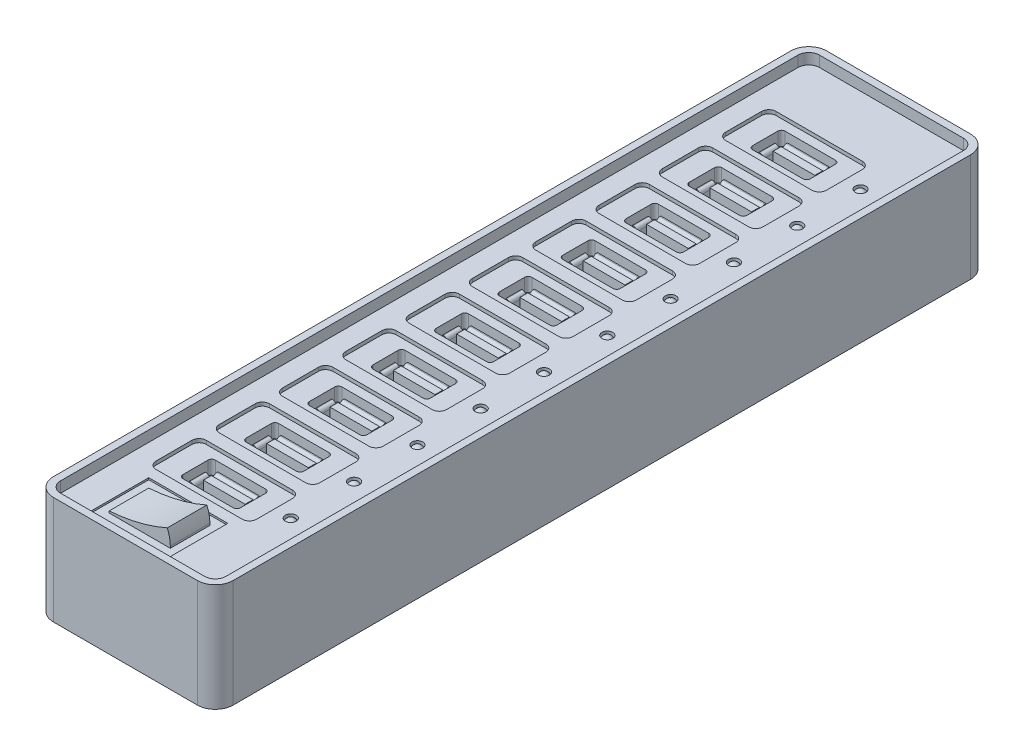
SolidWorks part; units mm, degrees
ref_plane "정면" through (0, 0, 0) normal (0, 0, 1) x (1, 0, 0)
ref_plane "윗면" through (0, 0, 0) normal (0, 1, 0) x (1, 0, 0)
ref_plane "우측면" through (0, 0, 0) normal (1, 0, 0) x (0, 0, -1)
sketch "스케치1" plane through (0, 0, 0) normal (0, 1, 0) x (1, 0, 0)
  line L1 (-20, -107.5) -> (20, -107.5)
  line L2 (-25, -102.5) -> (-25, 102.5)
  line L3 (-20, 107.5) -> (20, 107.5)
  line L4 (25, -102.5) -> (25, 102.5)
  line L5 (-25, -107.5) -> (25, 107.5) construction
  line L6 (-25, 107.5) -> (25, -107.5) construction
  arc A0 (20, -107.5) -> (25, -102.5) centre (20, -102.5) ccw
  arc A1 (-20, -107.5) -> (-25, -102.5) centre (-20, -102.5) cw
  arc A2 (20, 107.5) -> (25, 102.5) centre (20, 102.5) cw
  arc A3 (-25, 102.5) -> (-20, 107.5) centre (-20, 102.5) cw
  point P0 (0, 0)
  dimension "D3" = 5
  dimension "D1" = 215
  dimension "D2" = 50
extrude "보스-돌출1" add sketch "스케치1" along normal blind 30
sketch "스케치2" plane through (0, 30, 0) normal (0, 1, 0) x (1, 0, 0)
  line L0 (23, -102.5) -> (23, 102.5)
  line L1 (20, 105.5) -> (-20, 105.5)
  line L2 (-23, 102.5) -> (-23, -102.5)
  line L3 (-20, -105.5) -> (20, -105.5)
  arc A0 (20, -105.5) -> (23, -102.5) centre (20, -102.5) ccw
  arc A1 (23, 102.5) -> (20, 105.5) centre (20, 102.5) ccw
  arc A2 (-20, 105.5) -> (-23, 102.5) centre (-20, 102.5) ccw
  arc A3 (-23, -102.5) -> (-20, -105.5) centre (-20, -102.5) ccw
extrude "컷-돌출1" cut sketch "스케치2" against normal blind 3
sketch "스케치3" plane through (0, 27, 0) normal (0, 1, 0) x (1, 0, 0)
  line L0 (-25, 102.5) -> (-25, -102.5) construction
  line L1 (-15.5, -69.5) -> (8.5, -69.5)
  line L2 (-17.5, -71.5) -> (-17.5, -81.5)
  line L3 (-15.5, -83.5) -> (8.5, -83.5)
  line L4 (10.5, -71.5) -> (10.5, -81.5)
  line L5 (-17.5, -69.5) -> (10.5, -83.5) construction
  line L6 (-17.5, -83.5) -> (10.5, -69.5) construction
  line L7 (-20, -107.5) -> (20, -107.5) construction
  arc A0 (8.5, -83.5) -> (10.5, -81.5) centre (8.5, -81.5) ccw
  arc A1 (-17.5, -81.5) -> (-15.5, -83.5) centre (-15.5, -81.5) ccw
  arc A2 (8.5, -69.5) -> (10.5, -71.5) centre (8.5, -71.5) cw
  arc A3 (-15.5, -69.5) -> (-17.5, -71.5) centre (-15.5, -71.5) ccw
  point P0 (-3.5, -76.5)
  dimension "D5" = 2
  dimension "D1" = 28
  dimension "D2" = 14
  dimension "D3" = 7.5
  dimension "D4" = 24
extrude "컷-돌출2" cut sketch "스케치3" against normal blind 1
sketch "스케치4" plane through (0, 26, 0) normal (0, 1, 0) x (1, 0, 0)
  line L0 (10.5, -81.5) -> (10.5, -71.5) construction
  line L1 (-10.5, -72) -> (3.5, -72)
  line L2 (-11.5, -73) -> (-11.5, -80)
  line L3 (-10.5, -81) -> (3.5, -81)
  line L4 (4.5, -73) -> (4.5, -80)
  line L5 (-11.5, -72) -> (4.5, -81) construction
  line L6 (-11.5, -81) -> (4.5, -72) construction
  line L7 (-15.5, -83.5) -> (8.5, -83.5) construction
  arc A0 (3.5, -72) -> (4.5, -73) centre (3.5, -73) cw
  arc A1 (3.5, -81) -> (4.5, -80) centre (3.5, -80) ccw
  arc A2 (-11.5, -80) -> (-10.5, -81) centre (-10.5, -80) ccw
  arc A3 (-11.5, -73) -> (-10.5, -72) centre (-10.5, -73) cw
  point P0 (-3.5, -76.5)
  point P5 (4.5, -76.5)
  point P8 (10.5, -76.5)
  point P9 (-3.5, -72)
  point P12 (-3.5, -83.5)
  dimension "D3" = 1
  dimension "D1" = 16
  dimension "D2" = 9
extrude "컷-돌출3" cut sketch "스케치4" against normal blind 2
sketch "스케치5" plane through (0, 24, 0) normal (0, 1, 0) x (1, 0, 0)
  line L0 (2.3, -72.5) -> (-9.3, -72.5)
  line L1 (-11, -74.3) -> (-11, -78.7)
  line L2 (-9.3, -80.5) -> (2.3, -80.5)
  line L3 (4, -78.7) -> (4, -74.3)
  line L4 (3.5, -72) -> (-10.5, -72)
  line L5 (-11.5, -73) -> (-11.5, -80)
  line L6 (-10.5, -81) -> (3.5, -81)
  line L7 (4.5, -80) -> (4.5, -73)
  line L8 (3.5, -72) -> (-10.5, -72)
  line L9 (-11.5, -73) -> (-11.5, -80)
  line L10 (-10.5, -81) -> (3.5, -81)
  line L11 (4.5, -80) -> (4.5, -73)
  line L12 (-10, -74.3) -> (-11, -74.3)
  line L13 (-9.3, -79.2) -> (2.3, -79.2)
  line L14 (-9.8, -78.7) -> (-9.8, -74.3)
  line L15 (-9.3, -73.8) -> (2.3, -73.8)
  line L16 (2.8, -78.7) -> (2.8, -74.3)
  line L17 (-9.8, -79.2) -> (2.8, -73.8) construction
  line L18 (-9.8, -73.8) -> (2.8, -79.2) construction
  line L19 (-9.3, -73.6) -> (-9.3, -72.5)
  line L20 (-10, -78.7) -> (-11, -78.7)
  line L21 (-9.3, -79.4) -> (-9.3, -80.5)
  line L22 (2.3, -79.4) -> (2.3, -80.5)
  line L23 (3, -78.7) -> (4, -78.7)
  line L24 (3, -74.3) -> (4, -74.3)
  line L25 (2.3, -73.6) -> (2.3, -72.5)
  line L27 (3.5, -72.5) -> (-10.5, -72.5) construction
  line L28 (-11, -73) -> (-11, -80) construction
  line L29 (-10.5, -80.5) -> (3.5, -80.5) construction
  line L30 (4, -80) -> (4, -73) construction
  line L35 (-9.3, -76.5) -> (2.3, -78.7) construction
  line L36 (-9.3, -78.7) -> (2.3, -76.5) construction
  line L37 (-9.3, -76.5) -> (2.3, -76.5)
  line L38 (-9.3, -76.5) -> (-9.3, -74.3)
  line L39 (-9.3, -74.3) -> (2.3, -74.3)
  line L40 (2.3, -76.5) -> (2.3, -74.3)
  line L41 (-9.3, -76.5) -> (2.3, -74.3) construction
  line L42 (-9.3, -74.3) -> (2.3, -76.5) construction
  arc A4 (4.5, -73) -> (3.5, -72) centre (3.5, -73) ccw
  arc A5 (-10.5, -72) -> (-11.5, -73) centre (-10.5, -73) ccw
  arc A6 (-11.5, -80) -> (-10.5, -81) centre (-10.5, -80) ccw
  arc A7 (3.5, -81) -> (4.5, -80) centre (3.5, -80) ccw
  arc A8 (4.5, -73) -> (3.5, -72) centre (3.5, -73) ccw
  arc A9 (-10.5, -72) -> (-11.5, -73) centre (-10.5, -73) ccw
  arc A10 (-11.5, -80) -> (-10.5, -81) centre (-10.5, -80) ccw
  arc A11 (3.5, -81) -> (4.5, -80) centre (3.5, -80) ccw
  arc A12 (2.3, -73.8) -> (2.8, -74.3) centre (2.3, -74.3) cw
  arc A13 (2.3, -79.2) -> (2.8, -78.7) centre (2.3, -78.7) ccw
  arc A14 (-9.3, -79.2) -> (-9.8, -78.7) centre (-9.3, -78.7) cw
  arc A15 (-9.8, -74.3) -> (-9.3, -73.8) centre (-9.3, -74.3) cw
  arc A16 (-10.5, -72.5) -> (-11, -73) centre (-10.5, -73) ccw construction
  arc A17 (-11, -80) -> (-10.5, -80.5) centre (-10.5, -80) ccw construction
  arc A18 (3.5, -80.5) -> (4, -80) centre (3.5, -80) ccw construction
  arc A19 (4, -73) -> (3.5, -72.5) centre (3.5, -73) ccw construction
  arc A20 (-10, -74.3) -> (-9.3, -73.6) centre (-9.3, -74.3) cw
  arc A21 (-9.3, -79.4) -> (-10, -78.7) centre (-9.3, -78.7) cw
  arc A22 (2.3, -73.6) -> (3, -74.3) centre (2.3, -74.3) cw
  arc A23 (2.3, -79.4) -> (3, -78.7) centre (2.3, -78.7) ccw
  point P24 (-3.5, -76.5)
  point P30 (-3.5, -77.6)
  point P64 (-3.5, -76.5)
  point P65 (-3.5, -75.4)
  dimension "D5" = 0.5
  dimension "D3" = 12.6
  dimension "D4" = 5.4
  dimension "D1" = 0
  dimension "D2" = 0.5
  dimension "D6" = 0.2
  dimension "D7" = 0.2
  dimension "D8" = 0.2
extrude "컷-돌출4" cut sketch "스케치5" against normal blind 12
fillet "필렛1" radius 1 8 edges at (-9.6536, 24, 79.0536) (-3.5, 24, 79.2) (2.6536, 24, 79.0536) (2.8, 24, 76.5) (2.6536, 24, 73.9464) (-3.5, 24, 73.8) (-9.6536, 24, 73.9464) (-9.8, 24, 76.5)
sketch "스케치8" plane through (0, 0, 76.5) normal (0, 0, 1) x (1, 0, 0)
  line L0 (0, 0) -> (15, 0) construction
  line L1 (-20, 0) -> (20, 0) construction
  line L2 (15, 0) -> (15, 30) construction
  line L3 (-20, 30) -> (20, 30) construction
  line L4 (25, 30) -> (25, 0) construction
  line L7 (16.5, 27.5192) -> (15, 27.5192)
  line L8 (16.5, 25.5) -> (16.5, 27.5192)
  line L10 (15, 27.5192) -> (15, 27)
  arc A0 (16.5, 25.5) -> (15, 27) centre (15, 25.5) ccw
  dimension "D2" = 3
  dimension "D1" = 10
revolve "컷-회전1" cut sketch "스케치8" angle 360 about L2
pattern_linear "선형 패턴1" count 10 spacing 17.6 along (0, 0, -1) of "컷-돌출2", "컷-돌출3", "컷-돌출4", "필렛1", "컷-회전1"
sketch "스케치6" plane through (0, 27, 0) normal (0, 1, 0) x (1, 0, 0)
  line L0 (-20, -107.5) -> (20, -107.5) construction
  line L1 (-14.5, -102.5) -> (7.5, -102.5)
  line L2 (-14.5, -102.5) -> (-14.5, -86.5)
  line L3 (-14.5, -86.5) -> (7.5, -86.5)
  line L4 (7.5, -102.5) -> (7.5, -86.5)
  line L5 (-14.5, -102.5) -> (7.5, -86.5) construction
  line L6 (-14.5, -86.5) -> (7.5, -102.5) construction
  line L7 (-12, -100) -> (5, -100)
  line L8 (-12, -100) -> (-12, -89)
  line L9 (-12, -89) -> (5, -89)
  line L10 (5, -100) -> (5, -89)
  line L11 (-12, -100) -> (5, -89) construction
  line L12 (-12, -89) -> (5, -100) construction
  line L13 (-25, 102.5) -> (-25, -102.5) construction
  point P0 (-3.5, -94.5)
  point P5 (-3.5, -94.5)
  dimension "D1" = 22
  dimension "D2" = 16
  dimension "D3" = 2.5
  dimension "D4" = 2.5
  dimension "D5" = 5
  dimension "D6" = 10.5
extrude "컷-돌출5" cut sketch "스케치6" against normal blind 0.5
sketch "스케치7" plane through (0, 0, 100) normal (0, 0, 1) x (1, 0, 0)
  line L0 (-12, 27) -> (5, 27)
  arc A0 (5, 27) -> (4.1652, 31) centre (-5, 27) ccw
  arc A1 (-12, 27) -> (4.1652, 31) centre (-15.2723, 74.8883) ccw
  dimension "D1" = 10
  dimension "D3" = 48
  dimension "D2" = 4
extrude "보스-돌출2" add sketch "스케치7" against normal up to surface (11 mm away) up to face at (-3.5, 26.75, 89)
